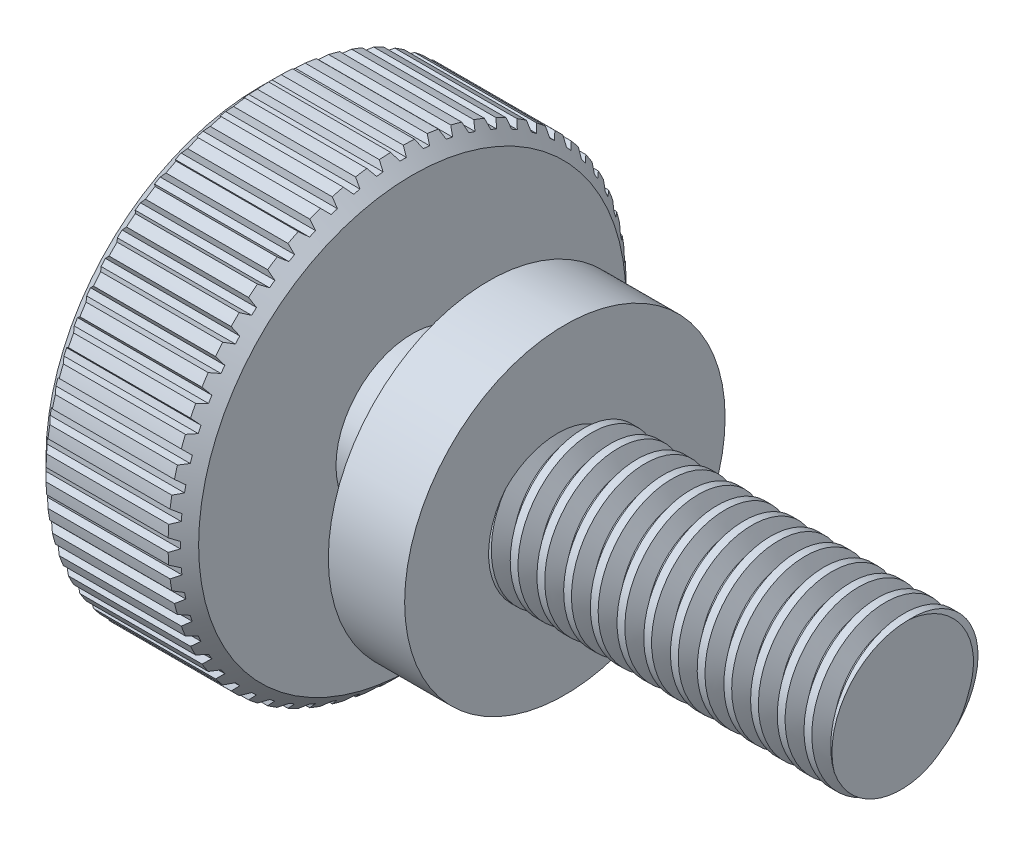
SolidWorks part; units mm, degrees
ref_plane "Front" through (0, 0, 0) normal (0, 0, 1) x (1, 0, 0)
ref_plane "Top" through (0, 0, 0) normal (0, 1, 0) x (1, 0, 0)
ref_plane "Right" through (0, 0, 0) normal (1, 0, 0) x (0, 0, -1)
sketch "Sketch1" plane through (0, 0, 0) normal (0, 0, 1) x (1, 0, 0)
  line L0 (-16.1137, 0) -> (18.4833, 0) construction
  line L1 (17, 0) -> (17, 2)
  line L2 (17, 2) -> (8, 2)
  line L3 (8, 2) -> (8, 4.2)
  line L4 (8, 4.2) -> (6, 4.2)
  line L5 (6, 4.2) -> (6, 2)
  line L6 (6, 2) -> (4, 2)
  line L7 (4, 2) -> (4, 6)
  line L8 (4, 6) -> (0, 6)
  line L9 (0, 6) -> (0, 0)
  line L10 (0, 0) -> (17, 0)
  dimension "D1" = 4.2
  dimension "D2" = 4
  dimension "D3" = 2
  dimension "D4" = 9
  dimension "D5" = 2
  dimension "D6" = 4
  dimension "D7" = 12
  dimension "D8" = 90
revolve "Revolve1" add sketch "Sketch1" angle 360 about L0
sketch "m4 thread profile" plane through (0, 0, 0) normal (0, 0, 1) x (1, 0, 0)
  line L0 (16.898, 2.1767) -> (17.248, 1.5705) construction
  line L1 (17.248, 1.5705) -> (17.598, 2.1767) construction
  line L2 (17.598, 2.1767) -> (16.898, 2.1767) construction
  line L4 (17, 0) -> (8, 0) construction
  line L5 (17.2095, 1.6372) -> (17.2865, 1.6372)
  line L6 (16.9902, 2.017) -> (17.2095, 1.6372)
  line L7 (16.9902, 2.017) -> (17.5058, 2.017)
  line L8 (17.5058, 2.017) -> (17.2865, 1.6372)
  point P3 (17.248, 2.1767)
  point P14 (17, 2)
  dimension "D1" = 0.7
  dimension "D2" = 60
  dimension "D3" = 1.5705
sketch "Sketch4" plane through (17, 0, 0) normal (1, 0, 0) x (0, 0, -1)
  circle A0 centre (0, 0) radius 2
  dimension "D1" = 4
curve "Helix/Spiral1" pitch 0.7 height 9 radius 2 centre (17, 0, 0) axis (-1, 0, 0) start towards (0, 1, 0)
sweep "Cut-Sweep1" cut profiles "m4 thread profile" path "Helix/Spiral1" align with end faces yes
chamfer "Chamfer1" distance 0.4 angle 45 2 edges at (4, 0, 6) (0, 0, 6)
sketch "Sketch5" plane through (0, 0, 0) normal (-1, 0, 0) x (0, 0, 1)
  line L0 (-0.2462, 6.159) -> (0, 5.67) construction
  line L1 (0, -6.5975) -> (0, 6.5975) construction
  line L2 (0, 5.67) -> (0.2462, 6.159) construction
  line L3 (0.2462, 6.159) -> (-0.2462, 6.159) construction
  line L4 (-0.0851, 5.839) -> (0.0851, 5.839)
  line L5 (0.0851, 5.839) -> (0.165, 5.9977)
  line L6 (-0.165, 5.9977) -> (-0.0851, 5.839)
  arc A1 (-0.165, 5.9977) -> (0.165, 5.9977) centre (0, 0) cw
  circle A2 centre (0, 0) radius 6 construction
  point P4 (0, 6.159)
  point P12 (0, 6)
  dimension "D1" = 0.33
  dimension "D2" = 0.33
  dimension "D3" = 0.161
extrude "Cut-Extrude1" cut sketch "Sketch5" against normal up to surface (4 mm away) up to face at (4, 0, 5.6)
pattern_circular "CirPattern1" count 60 over 360 about axis through (-16.1137, 0, 0) along (-1, 0, 0) of "Cut-Extrude1"
